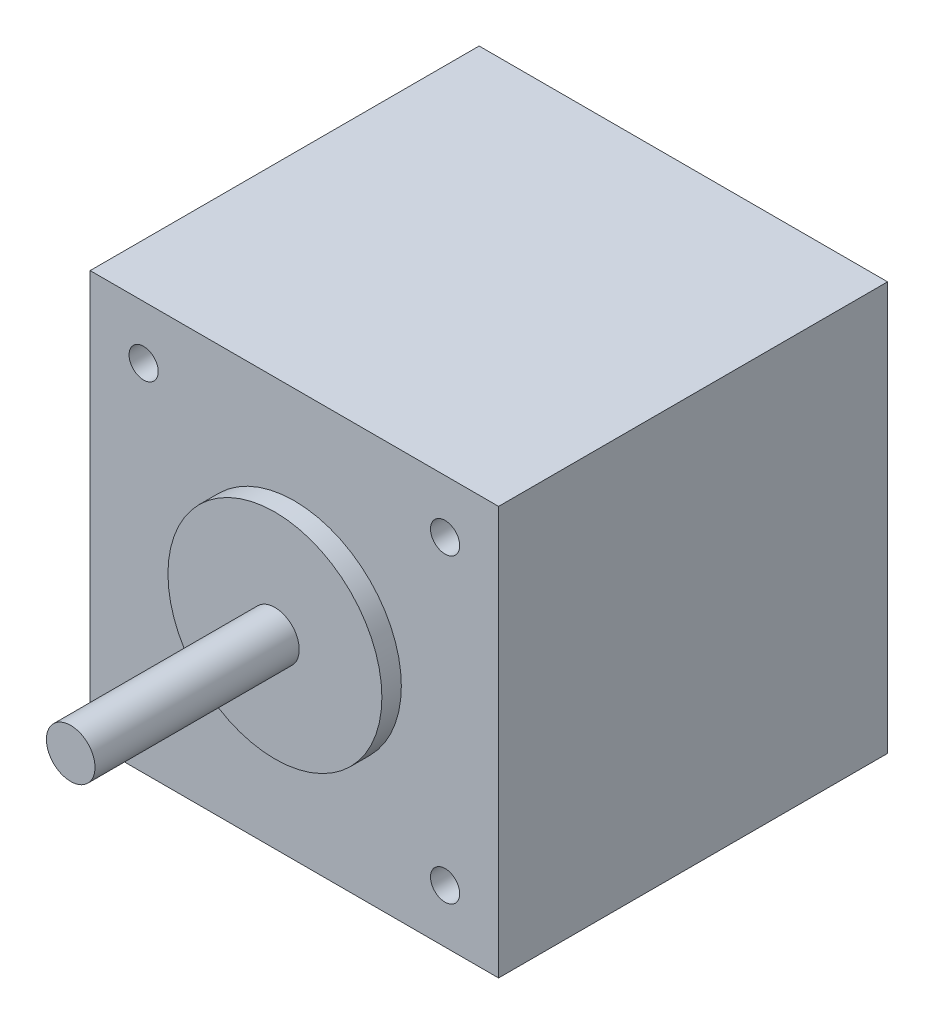
SolidWorks part; units mm, degrees
ref_plane "Спереди" through (0, 0, 0) normal (0, 0, 1) x (1, 0, 0)
ref_plane "Сверху" through (0, 0, 0) normal (0, 1, 0) x (1, 0, 0)
ref_plane "Справа" through (0, 0, 0) normal (1, 0, 0) x (0, 0, -1)
other "Configuration Table"
sketch "Эскиз1" plane through (0, 0, 0) normal (0, 0, 1) x (1, 0, 0)
  line L1 (-21, -21) -> (21, -21)
  line L2 (-21, -21) -> (-21, 21)
  line L3 (-21, 21) -> (21, 21)
  line L4 (21, -21) -> (21, 21)
  line L5 (-21, -21) -> (21, 21) construction
  line L6 (-21, 21) -> (21, -21) construction
  point P0 (0, 0)
  dimension "D1" = 42
  dimension "D2" = 42
extrude "Корпус" add sketch "Эскиз1" along normal blind 40
sketch "Эскиз2" plane through (0, 0, 0) normal (0, 0, 1) x (1, 0, 0)
  circle A0 centre (0, 0) radius 2.5
extrude "Вал_ПРЕДВ" add sketch "Эскиз2" along normal blind 63
sketch "Эскиз3" plane through (0, 0, 0) normal (0, 0, 1) x (1, 0, 0)
  circle A0 centre (0, 0) radius 11
  dimension "D1" = 22
extrude "Буртик_ПРЕДВ" add sketch "Эскиз3" along normal blind 42
sketch "Эскиз4" plane through (0, 0, 0) normal (0, 0, 1) x (1, 0, 0)
  circle A0 centre (-15.5, -15.5) radius 1.5
  circle A1 centre (-15.5, 15.5) radius 1.5
  circle A2 centre (15.5, -15.5) radius 1.5
  circle A3 centre (15.5, 15.5) radius 1.5
  dimension "D1" = 3
  dimension "D2" = 3
  dimension "D3" = 3
  dimension "D4" = 3
extrude "Крепеж_М3_ПРЕДВ" cut sketch "Эскиз4" against normal blind 4.5 from offset 40
equation "\"Мотор X ширина корпуса\"= 42.3"
equation "\"Мотор X высота корпуса\"= 42.3"
equation "\"Мотор X длина корпуса\"= 40"
equation "\"Мотор X вылет вала\"= 19.8"
equation "\"Мотор Y ширина корпуса\"= 42.3"
equation "\"Мотор Y высота корпуса\"= 42.3"
equation "\"Мотор Y длина корпуса\"= 48"
equation "\"Мотор Y вылет вала\"= 30"
equation "\"Мотор Z ширина корпуса\"= 42"
equation "\"Мотор Z высота корпуса\"= 42"
equation "\"Мотор Z длина корпуса\"= 40"
equation "\"Мотор Z вылет вала\"= 23"
equation "\"Мотор диаметр вала ПРЕДВ\"= 5"
equation "\"Мотор шаг крепления ПРЕДВ\"= 31"
equation "\"Мотор диаметр отверстий ПРЕДВ\"= 3"
equation "\"Мотор глубина отверстий ПРЕДВ\"= 4.5"
equation "\"Мотор диаметр буртика ПРЕДВ\"= 22"
equation "\"Мотор высота буртика ПРЕДВ\"= 2"
equation "\"Мотор диаметр шкива ПРЕДВ\"= 16"
equation "\"Мотор длина шкива ПРЕДВ\"= 12"
equation "\"Мотор отступ шкива ПРЕДВ\"= 5"
equation "\"Мотор X шаг градусов\"= 1.8"
equation "\"Мотор X ток А\"= 1.5"
equation "\"Мотор X сопротивление Ом\"= 1.3"
equation "\"Мотор X индуктивность мГн\"= 2"
equation "\"Мотор Y шаг градусов\"= 1.8"
equation "\"Мотор Y ток А\"= 2.2"
equation "\"Мотор Y сопротивление Ом\"= 0.9"
equation "\"Мотор Y индуктивность мГн\"= 2"
equation "\"Мотор Z шаг градусов\"= 1.8"
equation "\"Мотор Z ток А\"= 1"
equation "\"Мотор Z сопротивление Ом\"= 4"
equation "\"Мотор Z индуктивность мГн\"= 8"
equation "\"Мотор Y диаметр ротора\"= 25.78"
equation "\"D1@Эскиз1\" = \"Мотор Z ширина корпуса\""
equation "\"D2@Эскиз1\" = \"Мотор Z высота корпуса\""
equation "\"D1@Корпус\" = \"Мотор Z длина корпуса\""
equation "\"D1@Эскиз2\" = \"Мотор диаметр вала ПРЕДВ\""
equation "\"D1@Вал_ПРЕДВ\" = \"Мотор Z длина корпуса\" + \"Мотор Z вылет вала\""
equation "\"D1@Эскиз3\" = \"Мотор диаметр буртика ПРЕДВ\""
equation "\"D1@Буртик_ПРЕДВ\" = \"Мотор Z длина корпуса\" + \"Мотор высота буртика ПРЕДВ\""
equation "\"D1@Эскиз4\" = \"Мотор диаметр отверстий ПРЕДВ\""
equation "\"D2@Эскиз4\" = \"Мотор диаметр отверстий ПРЕДВ\""
equation "\"D3@Эскиз4\" = \"Мотор диаметр отверстий ПРЕДВ\""
equation "\"D4@Эскиз4\" = \"Мотор диаметр отверстий ПРЕДВ\""
equation "\"D1@Крепеж_М3_ПРЕДВ\" = \"Мотор глубина отверстий ПРЕДВ\""
equation "\"D19@Крепеж_М3_ПРЕДВ\" = \"Мотор Z длина корпуса\""
equation "\"Ширина груза\"= 420"
equation "\"Глубина груза\"= 490"
equation "\"Высота груза\"= 297"
equation "\"Ширина ячейки\"= \"Ширина груза\" + 10"
equation "\"Глубина ячейки\"= \"Глубина груза\" + 10"
equation "\"Высота ячейки\"= \"Высота груза\" + 10 + 13"
equation "\"Колво ячеек ширина\"= 2"
equation "\"Колво ячеек высота\"= 2"
equation "\"Толщина стенки\" = \"Толщина тонких панелей\""
equation "\"Крепление дверцы\"= 5 "
equation "\"Ширина рейки\"= \"Толщина шестерни\""
equation "\"Высота рейки\"= 20"
equation "\"Высота пола\" = 2*\"Толщина тонких панелей\""
equation "\"Колво полозьев\"= 5"
equation "\"Отступ рейки\"= 20"
equation "\"Глубина каретки\"= \"Глубина ячейки\" + 30 + \"Мотор Y высота корпуса\" + 20"
equation "\"Отступ шпильки\"= 26"
equation "\"Диаметр шпильки\"= 5"
equation "\"Длинна шпильки\" = (\"Высота ячейки\"+\"Толщина горизонтальных плит\"+\"Высота пола\")*\"Колво ячеек высота\"+2*(\"Толщина горизонтальных плит\"+\"Отступ рейки\")"
equation "\"Ширина пластины\"= 50  "
equation "\"Высота зона выгрузки\"= \"Высота ячейки\" * 2 + \"Толщина стенки\" * 2"
equation "\"Колво выгрузки\"= 1"
equation "\"Отступ крепления мотора фиксации\" = (\"Ширина пластины\"+20-\"Толщина вертикальных стенок\")/2"
equation "\"Диаметр оси\"= 10"
equation "\"Диаметр ролика\"= 20"
equation "\"Колво роликов\"= 10"
equation "\"Шаг роликов\"= \"Диаметр ролика\" + 20"
equation "\"Ширина ячейки выгрузки\" = \"Ширина ячейки\"+\"Толщина вертикальных стенок\"+2*\"Отступ крепления мотора фиксации\""
equation "\"Длинна рейки\" = (\"Ширина ячейки\"+\"Толщина вертикальных стенок\"+\"Крепление дверцы\")*\"Колво ячеек ширина\"+\"Ширина ячейки выгрузки\"*\"Колво выгрузки\"+\"Толщина вертикальных стенок\"+2*\"Отступ крепления мотора фиксации\"-\"Крепление дверцы\"*\"Колво ячеек ширина\""
equation "\"Толщина тонких панелей\"= 6"
equation "\"Толщина вертикальных стенок\"= 18"
equation "\"Толщина горизонтальных плит\"= 18"
equation "\"Базовая высота корпуса\"= (\"Высота ячейки\"+\"Толщина тонких панелей\"+\"Высота пола\")*\"Колво ячеек высота\"+6*\"Толщина тонких панелей\"+\"Мотор X ширина корпуса\"+\"Мотор Y ширина корпуса\"+75"
equation "\"Высота корпуса\"= (\"Высота ячейки\"+\"Толщина горизонтальных плит\"+\"Высота пола\")*\"Колво ячеек высота\"+2*\"Толщина горизонтальных плит\"+4*\"Толщина тонких панелей\"+\"Мотор X ширина корпуса\"+\"Мотор Y ширина корпуса\"+75"
equation "\"Смещение центра корпуса\"= (\"Высота корпуса\"-\"Базовая высота корпуса\")/2-(\"Толщина горизонтальных плит\"-\"Толщина тонких панелей\")"
equation "\"Отметка пола\"= -\"Базовая высота корпуса\"/2+\"Толщина тонких панелей\""
equation "\"Отметка потолка\"= \"Отметка пола\"+\"Высота корпуса\"-2*\"Толщина горизонтальных плит\""
equation "\"Отметка верхней полки\"= \"Отметка потолка\"-(28+\"Толщина тонких панелей\")-\"Высота ячейки\"-\"Высота пола\""
equation "\"Отметка нижней полки\"= \"Отметка верхней полки\"-\"Высота ячейки\"-\"Высота пола\"-\"Толщина горизонтальных плит\""
